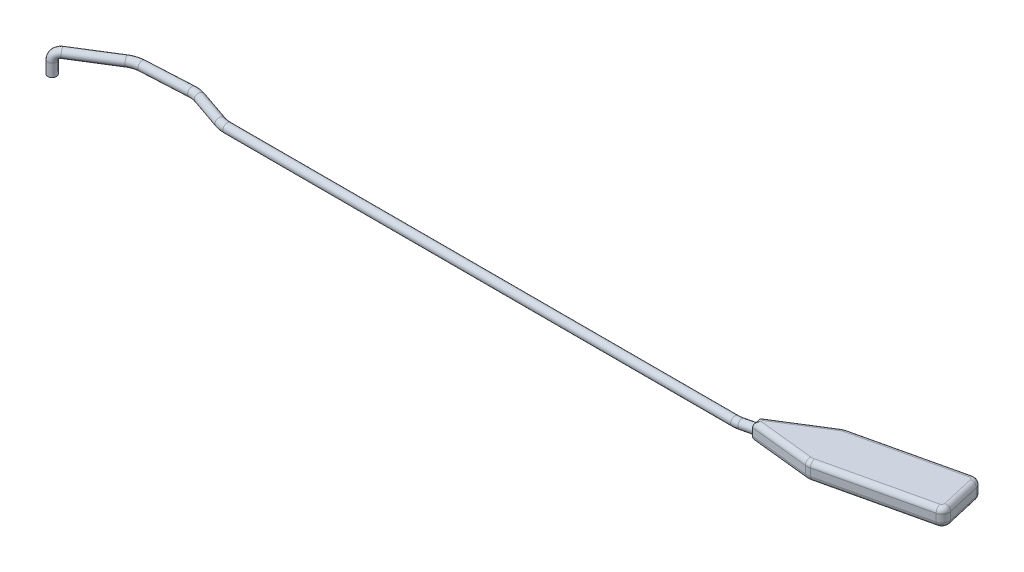
SolidWorks part; units mm, degrees
ref_plane "Front Plane" through (0, 0, 0) normal (0, 0, 1) x (1, 0, 0)
ref_plane "Top Plane" through (0, 0, 0) normal (0, 1, 0) x (1, 0, 0)
ref_plane "Right Plane" through (0, 0, 0) normal (1, 0, 0) x (0, 0, -1)
sketch "Sketch1" plane through (0, 0, 0) normal (0, 1, 0) x (1, 0, 0)
  line L4 (0, 0) -> (-4.7361, -1.0934)
  line L5 (-6.9856, -1.3497) -> (-210.6728, -1.3497)
  line L6 (-213.9285, -0.8049) -> (-226.5821, 3.5521)
  line L7 (-230.3612, 4.0832) -> (-249.3052, 3.0904)
  line L8 (-254.081, 1.5846) -> (-268.8488, -7.6433)
  arc A3 (-254.081, 1.5846) -> (-249.3052, 3.0904) centre (-248.7818, -6.8959) cw
  arc A4 (-230.3612, 4.0832) -> (-226.5821, 3.5521) centre (-229.8378, -5.9031) cw
  arc A5 (-213.9285, -0.8049) -> (-210.6728, -1.3497) centre (-210.6728, 8.6503) ccw
  arc A6 (-6.9856, -1.3497) -> (-4.7361, -1.0934) centre (-6.9856, 8.6503) ccw
  point P1 (-272.4106, -9.869)
  point P13 (-251.8878, 2.9551)
  point P18 (-228.42, 4.185)
  point P21 (-212.3462, -1.3497)
  point P24 (-5.8462, -1.3497)
  dimension "D7" = 161
  dimension "D8" = 158
  dimension "D9" = 151
  dimension "D11" = 10
  dimension "D1" = 6
  dimension "D2" = 167
  dimension "D3" = 206.5
  dimension "D4" = 17
  dimension "D5" = 23.5
  dimension "D6" = 20
  dimension "D10" = 24.2
sketch3d "3DSketch2"
  line L0 (-272.4106, -3, 9.869) -> (-272.4106, -8, 9.869)
  line L1 (-269.8664, 0, 8.2792) -> (-268.8488, 0, 7.6433)
  arc A0 (-269.8664, 0, 8.2792) -> (-272.4106, -3, 9.869) centre (-269.8664, -3, 8.2792) ccw
  point P0 (-272.4106, 0, 9.869)
  point P9 (-272.4106, 0, 9.869)
  point P10 (-268.2767, -3, 10.8234)
  dimension "D2" = 3
  dimension "D1" = 8
ref_plane "Plane3" through (0, 0, 0) normal (-0.9744, 0, 0.225) x (0.225, 0, 0.9744)
sketch "Sketch11" plane through (0, 0, 0) normal (-0.9744, 0, 0.225) x (0.225, 0, 0.9744)
  circle A0 centre (0, 0) radius 1.75
  dimension "D1" = 3.5
sweep "Sweep1" add profiles "Sketch11" path "Sketch1"
sketch "Sketch3" plane through (0, 0, 0) normal (0, 1, 0) x (1, 0, 0)
  line L0 (0, 0) -> (-4.7361, -1.0934) construction
  line L2 (8.1234, 8.2898) -> (40.7356, 15.8189)
  line L3 (43.5474, 3.6393) -> (10.9352, -3.8898)
  line L4 (7.971, -3.8223) -> (0.3937, -1.7051)
  line L5 (0, 0) -> (32.6224, 7.5315) construction
  line L6 (5.4887, 6.9297) -> (-0.3937, 1.7051)
  line L7 (-0.6014, 2.6048) -> (0.6014, -2.6048) construction
  line L8 (-0.3937, 1.7051) -> (-5.1297, 0.6117) construction
  line L9 (-4.3424, -2.7986) -> (0.3937, -1.7051) construction
  arc A0 (43.5474, 3.6393) -> (40.7356, 15.8189) centre (42.1415, 9.7291) ccw
  arc A1 (8.1234, 8.2898) -> (5.4887, 6.9297) centre (9.4731, 2.4436) ccw
  arc A2 (10.9352, -3.8898) -> (7.971, -3.8223) centre (9.5855, 1.9564) cw
  point P11 (6.6326, 7.9457)
  point P18 (9.4445, -4.234)
  dimension "D2" = 35
  dimension "D4" = 6
  dimension "D6" = 6.25
  dimension "D7" = 6
  dimension "D11" = 43.25
  dimension "D3" = 12.5
  dimension "D5" = 35
sketch "Sketch8" plane through (-196.7871, 0, 122.9662) normal (-0.848, 0, 0.5299) x (0.5299, 0, 0.848)
  circle A0 centre (-135.9862, 0) radius 1.75
  dimension "D1" = 3.5
sweep "Sweep3" add profiles "Sketch8" path "3DSketch2"
ref_plane "Plane1" through (-0.3937, 0, -1.7051) normal (0.7477, 0, -0.6641) x (-0.6641, 0, -0.7477)
sketch "Sketch5" plane through (0, 0, 0) normal (0, 1, 0) x (1, 0, 0)
  line L0 (-0.3937, 1.7051) -> (19.8139, 14.3709)
  line L1 (21.6507, 15.1332) -> (62.5742, 24.5811)
  line L2 (67.017, 5.3373) -> (26.0935, -4.1106)
  line L3 (24.1084, -4.2306) -> (0.3937, -1.7051)
  line L4 (-0.6014, 2.6048) -> (0.6014, -2.6048) construction
  line L6 (69.2653, 8.9353) -> (66.1722, 22.3329)
  line L8 (0, 0) -> (32.6224, 7.5315) construction
  line L14 (-0.3937, 1.7051) -> (0.3937, -1.7051)
  arc A0 (67.017, 5.3373) -> (69.2653, 8.9353) centre (66.3421, 8.2605) ccw
  arc A1 (19.8139, 14.3709) -> (21.6507, 15.1332) centre (23.0004, 9.287) cw
  arc A2 (24.1084, -4.2306) -> (26.0935, -4.1106) centre (24.7438, 1.7356) ccw
  arc A3 (62.5742, 24.5811) -> (66.1722, 22.3329) centre (63.2491, 21.658) cw
  dimension "D2" = 6
  dimension "D3" = 6
  dimension "D6" = 3
  dimension "D1" = 19.75
  dimension "D4" = 69.5
  dimension "D5" = 45
  dimension "D7" = 9.875
  dimension "D8" = 45
extrude "Boss-Extrude1" add sketch "Sketch5" along normal mid plane 7
sketch "Sketch10" plane through (0, -8, 0) normal (0, -1, 0) x (1, 0, 0)
  circle A0 centre (-272.4106, 9.869) radius 1.75 construction
  point P0 (-274.1258, 9.5217)
fillet "Fillet1" radius 2 10 edges at (42.1124, 3.5, -19.8572) (64.8388, 3.5, -24.2022) (67.7187, 3.5, -15.6341) (68.8863, 3.5, -6.6707) (46.5552, 3.5, -0.6134) (25.1059, 3.5, 4.2534) (12.251, 3.5, 2.9679) (0, 3.5, 0) (9.7101, 3.5, -8.038) (20.7005, 3.5, -14.8287)
fillet "Fillet2" radius 2 10 edges at (9.7101, -3.5, -8.038) (0, -3.5, 0) (12.251, -3.5, 2.9679) (25.1059, -3.5, 4.2534) (46.5552, -3.5, -0.6134) (68.8863, -3.5, -6.6707) (67.7187, -3.5, -15.6341) (64.8388, -3.5, -24.2022) (42.1124, -3.5, -19.8572) (20.7005, -3.5, -14.8287)
